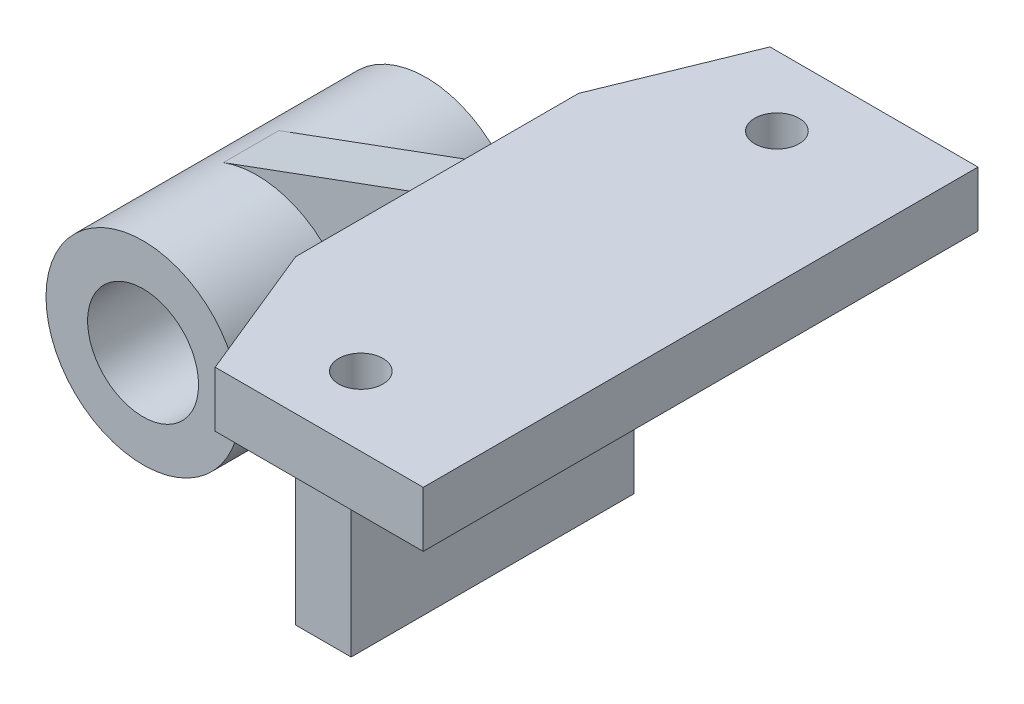
SolidWorks part; units mm, degrees
ref_plane "Front Plane" through (0, 0, 0) normal (0, 0, 1) x (1, 0, 0)
ref_plane "Top Plane" through (0, 0, 0) normal (0, 1, 0) x (1, 0, 0)
ref_plane "Right Plane" through (0, 0, 0) normal (1, 0, 0) x (0, 0, -1)
sketch "Sketch1" plane through (0, 0, 0) normal (0, 0, 1) x (1, 0, 0)
  line L0 (-2.4145, -6.5704) -> (11, -11.5)
  line L1 (15, -11.5) -> (15, 7.5)
  line L2 (15, -11.5) -> (11, -11.5)
  line L3 (-2.4145, 6.5704) -> (11, 11.5)
  line L4 (30, 7.5) -> (30, 11.5)
  line L5 (15, 7.5) -> (30, 7.5)
  line L6 (11, 11.5) -> (30, 11.5)
  line L7 (11, 11.5) -> (11, -11.5) construction
  arc A0 (-2.4145, 6.5704) -> (-2.4145, -6.5704) centre (0, 0) ccw
  circle A1 centre (0, 0) radius 4
  point P10 (0, 0)
  dimension "D1" = 8
  dimension "D2" = 7
  dimension "D3" = 4
  dimension "D4" = 15
  dimension "D5" = 7.5
  dimension "D6" = 15
  dimension "D7" = 4
  dimension "D8" = 11.5
extrude "Boss-Extrude1" add sketch "Sketch1" along normal blind 20.4
ref_plane "Plane1" through (0, 0, 10.2) normal (0, 0, 1) x (1, 0, 0)
sketch "Sketch5" plane through (0, 0, 10.2) normal (0, 0, 1) x (1, 0, 0)
  line L0 (11, 11.5) -> (11, 2)
  line L1 (-2.4145, 6.5704) -> (11, 11.5)
  line L2 (6.7082, 2) -> (11, -2) construction
  line L3 (6.7082, 2) -> (11, 2)
  line L5 (6.7082, -2) -> (11, -2)
  line L6 (11, 2) -> (11, -2)
  line L9 (11, -11.5) -> (-2.4145, -6.5704)
  line L11 (11, -2) -> (11, -11.5)
  line L12 (11, 11.5) -> (11, 2)
  circle A0 centre (0, 0) radius 7 construction
  arc A1 (-2.4145, -6.5704) -> (6.7082, -2) centre (0, 0) ccw
  arc A2 (-2.4145, 6.5704) -> (6.7082, 2) centre (0, 0) cw
  point P13 (8.8541, 0)
  point P14 (0, 0)
  point P19 (0, 0)
  dimension "D1" = 4
extrude "Cut-Extrude3" cut sketch "Sketch5" against normal through all from offset 2 contours L1 A2 L3 L0 | A1 L9 L11 L5 region at (7.355, -6.5849, 10.2) region at (7.355, 6.5849, 10.2) offset against normal yes
extrude "Cut-Extrude4" cut sketch "Sketch5<5>" along normal through all from offset 2 contours L1 A2 L3 L0 | A1 L9 L11 L5 region at (7.355, -6.5849, 10.2) region at (7.355, 6.5849, 10.2)
sketch "Sketch5<5>" plane through (0, 0, 10.2) normal (0, 0, 1) x (1, 0, 0) same geometry as "Sketch5"
sketch "Sketch6" plane through (0, 11.5, 0) normal (0, 1, 0) x (1, 0, 0)
  line L0 (11, -12.2) -> (11, -8.2) construction
  line L1 (14.9993, 9.8) -> (30, 9.8)
  line L2 (11, 0) -> (11, -20.4)
  line L3 (14.9993, -30.2) -> (30, -30.2)
  line L4 (30, 9.8) -> (30, -30.2)
  line L5 (30, -20.4) -> (30, 0) construction
  line L6 (11, -20.4) -> (14.9993, -30.2)
  line L7 (11, 0) -> (14.9993, 9.8)
  line L8 (11, -10.2) -> (30, -10.2) construction
  line L9 (-12.65, -10.2) -> (12.65, -10.2) construction
  point P16 (30, -10.2)
  dimension "D1" = 40
  dimension "D2" = 112.2
  dimension "D3" = 112.2
extrude "Boss-Extrude2" add sketch "Sketch6" against normal blind 4
sketch "Sketch7" plane through (0, 11.5, 0) normal (0, 1, 0) x (1, 0, 0)
  line L0 (20.5, -25.2) -> (20.5, 4.8) construction
  line L1 (11, -10.2) -> (30, -10.2) construction
  line L2 (11, -12.2) -> (11, -8.2) construction
  line L3 (30, -30.2) -> (30, 9.8) construction
  circle A0 centre (20.5, 4.8) radius 1.6
  circle A1 centre (20.5, -25.2) radius 1.6
  point P10 (37.6957, -22.4865)
  point P11 (20.5, -10.2)
  point P12 (20.5, -10.2)
  dimension "D1" = 3.2
  dimension "D2" = 30
extrude "Cut-Extrude5" cut sketch "Sketch7" against normal up to next
